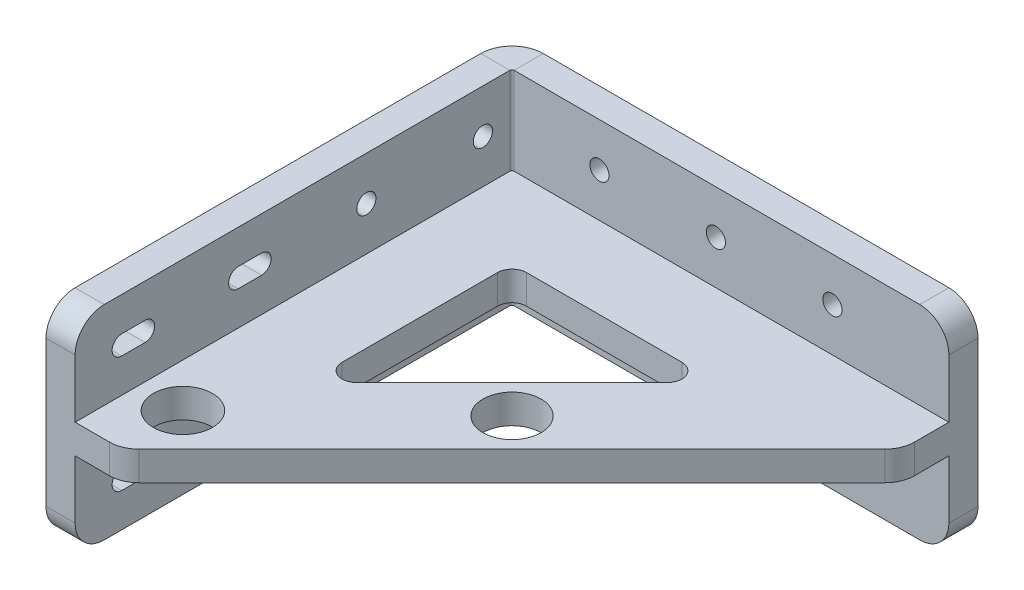
SolidWorks part; units mm, degrees
note: The reader was unsure of these and kept them because the rebuilt part matched: thickness of "基体-法兰1", "边线-法兰1", "钣金6", "钣金7", "钣金8", "钣金9", "钣金10", "钣金11", "钣金12"; flange length of "边线-法兰1".
ref_plane "前视基准面" through (0, 0, 0) normal (0, 0, 1) x (1, 0, 0)
ref_plane "上视基准面" through (0, 0, 0) normal (0, 1, 0) x (1, 0, 0)
ref_plane "右视基准面" through (0, 0, 0) normal (1, 0, 0) x (0, 0, -1)
sketch "草图1" plane through (0, 0, 0) normal (0, 0, 1) x (1, 0, 0)
  line L1 (-80, 35) -> (80, 35)
  line L2 (-80, 35) -> (-80, -35)
  line L3 (-80, -35) -> (80, -35)
  line L4 (80, 35) -> (80, -35)
  line L5 (-80, 35) -> (80, -35) construction
  line L6 (-80, -35) -> (80, 35) construction
  point P0 (0, 0)
  dimension "D1" = 160
  dimension "D2" = 70
base flange "基体-法兰1" sketch "草图1" thickness 10 reverse thickness direction no parameters "D1"=0.7366
edge flange "边线-法兰1" sketch "草图8" flange angle 90 flange length 160 flange position material inside bend radius 0.7366 thickness 10 relief rectangular parameters "D6"=10
sketch "草图8" plane through (-80, 0, 0) normal (-1, 0, 0) x (0, -1, 0)
  line L0 (-35, 0) -> (35, 0) construction
  line L1 (-35, 0) -> (35, 0)
  line L2 (-35, 0) -> (-35, 150)
  line L3 (-35, 150) -> (35, 150)
  line L4 (35, 150) -> (35, 0)
bend "边线折弯1" bend radius 0.7366 bend angle 90 parameters "D5"=1
sketch "草图9" plane through (0, 0, 0) normal (0, 1, 0) x (1, 0, 0)
  line L0 (-70, -150) -> (-54, -150)
  line L1 (-54, -150) -> (80, -16)
  line L2 (80, 0) -> (80, -16)
  line L3 (80, 0) -> (-69.2634, 0) construction
  line L4 (-70, -150) -> (-70, -0.7366) construction
  line L5 (80, 0) -> (-69.2634, 0)
  line L6 (-70, -150) -> (-70, -0.7366)
  arc A0 (-69.2634, 0) -> (-70, -0.7366) centre (-69.2634, -0.7366) ccw construction
  arc A1 (-69.2634, 0) -> (-70, -0.7366) centre (-69.2634, -0.7366) ccw
  dimension "D1" = 16
extrude "凸台-拉伸1" add sketch "草图9" along normal mid plane 10
fillet "圆角1" radius 10 6 edges at (80, -35, -5) (80, 35, -5) (-75, -35, 150) (-75, 35, 150) (80, 0, 16) (-54, 0, 150)
sketch "草图10" plane through (0, 5, 0) normal (0, 1, 0) x (1, 0, 0)
  line L10 (-42, -98.402) -> (28.402, -28)
  line L11 (28.402, -28) -> (-42, -28)
  line L12 (-42, -28) -> (-42, -98.402)
  line L13 (-42, -98.402) -> (28.402, -28)
  line L14 (28.402, -28) -> (-42, -28)
  line L15 (-42, -28) -> (-42, -98.402)
  dimension "D1" = 28
extrude "切除-拉伸1" cut sketch "草图10" against normal blind 10 normal cut yes
fillet "圆角2" radius 5 3 edges at (28.402, 0, 28) (-42, 0, 28) (-42, 0, 98.402)
sketch "草图11" plane through (-70, 0, 0) normal (1, 0, 0) x (0, 0, -1)
  line L0 (10, 35.5) -> (10, 25.4) construction
  line L1 (-70, 35.5) -> (-70, 25.4) construction
  line L2 (10, 35.5) -> (10, 25.4) construction
  line L3 (-70, 35.5) -> (-70, 25.4) construction
  line L4 (-125.9, 40) -> (-125.9, -790) construction
  line L5 (-134.1, 40) -> (-134.1, -790) construction
  line L6 (-94.1, 40) -> (-94.1, -790) construction
  line L7 (-85.9, 40) -> (-85.9, -790) construction
  line L8 (-125.9, 35) -> (-125.9, -35) construction
  line L9 (-134.1, 35) -> (-134.1, -35) construction
  line L10 (-94.1, 35) -> (-94.1, -35) construction
  line L11 (-85.9, 35) -> (-85.9, -35) construction
  line L12 (-70, 30.45) -> (10, 30.45) construction
  line L13 (-0.7366, -35) -> (-140, -35) construction
  line L14 (-140, 35) -> (-0.7366, 35) construction
  line L15 (-134.1, 0) -> (-125.9, 0) construction
  line L16 (-94.1, 0) -> (-85.9, 0) construction
  line L17 (-30, 30.45) -> (-30, 0) construction
  line L18 (0, 0) -> (-30, 0) construction
  line L19 (-130, -20) -> (-130, 20) construction
  line L20 (-90, -20) -> (-90, 20) construction
  line L21 (-10, 0) -> (-50, 0) construction
  line L22 (-50, -20) -> (-50, 20) construction
  line L23 (-10, -20) -> (-10, 20) construction
  line L24 (-134, 20) -> (-126, 20) construction
  line L25 (-134, 23.3) -> (-126, 23.3)
  line L26 (-134, 16.7) -> (-126, 16.7)
  line L27 (-86, 20) -> (-94, 20) construction
  line L28 (-86, 16.7) -> (-94, 16.7)
  line L29 (-86, 23.3) -> (-94, 23.3)
  line L30 (-86, -20) -> (-94, -20) construction
  line L31 (-86, -23.3) -> (-94, -23.3)
  line L32 (-86, -16.7) -> (-94, -16.7)
  line L33 (-126, -20) -> (-134, -20) construction
  line L34 (-126, -23.3) -> (-134, -23.3)
  line L35 (-126, -16.7) -> (-134, -16.7)
  circle A0 centre (-50, 20) radius 3.3
  circle A1 centre (-10, 20) radius 3.3
  circle A2 centre (-10, -20) radius 3.3
  circle A3 centre (-50, -20) radius 3.3
  arc A4 (-134, 23.3) -> (-134, 16.7) centre (-134, 20) ccw
  arc A5 (-126, 16.7) -> (-126, 23.3) centre (-126, 20) ccw
  arc A6 (-86, 16.7) -> (-86, 23.3) centre (-86, 20) ccw
  arc A7 (-94, 23.3) -> (-94, 16.7) centre (-94, 20) ccw
  arc A8 (-86, -23.3) -> (-86, -16.7) centre (-86, -20) ccw
  arc A9 (-94, -16.7) -> (-94, -23.3) centre (-94, -20) ccw
  arc A10 (-126, -23.3) -> (-126, -16.7) centre (-126, -20) ccw
  arc A11 (-134, -16.7) -> (-134, -23.3) centre (-134, -20) ccw
  point P32 (-130, 0)
  point P40 (-90, 0)
  point P43 (-30, 0)
  point P46 (-50, 0)
  point P49 (-10, 0)
  point P55 (-130, 20)
  point P61 (-90, 20)
  point P68 (-90, -20)
  point P75 (-130, -20)
  dimension "D3" = 6.6
  dimension "D1" = 40
  dimension "D2" = 40
  dimension "D4" = 6.6
  dimension "D5" = 8
extrude "切除-拉伸2" cut sketch "草图11" against normal blind 10 normal cut yes
sketch "草图12" plane through (0, 0, 0) normal (0, 0, 1) x (1, 0, 0)
  line L0 (40, 0) -> (-40, 0) construction
  line L1 (-40, -20) -> (-40, 20) construction
  line L2 (40, -20) -> (40, 20) construction
  line L3 (0, -20) -> (0, 20) construction
  circle A0 centre (-40, -20) radius 3.3
  circle A1 centre (-40, 20) radius 3.3
  circle A2 centre (40, 20) radius 3.3
  circle A3 centre (40, -20) radius 3.3
  circle A4 centre (0, -20) radius 3.3
  circle A5 centre (0, 20) radius 3.3
  point P4 (0, 0)
  point P8 (-40, 0)
  point P11 (40, 0)
  point P18 (0, 0)
  dimension "D3" = 6.6
  dimension "D1" = 80
  dimension "D2" = 40
extrude "切除-拉伸3" cut sketch "草图12" against normal blind 10 normal cut yes
sketch "草图13" plane through (0, 5, 0) normal (0, 1, 0) x (1, 0, 0)
  line L2 (-6.799, -63.201) -> (13, -83) construction
  line L3 (-33.4645, -89.8665) -> (19.8665, -36.5355) construction
  line L4 (-51.0711, -147.0711) -> (77.0711, -18.9289) construction
  line L5 (-80, -140) -> (-80, -0.7366) construction
  line L6 (-70, -150) -> (-58.1421, -150) construction
  circle A0 centre (3.1005, -73.1005) radius 10
  circle A1 centre (-55, -128) radius 10.1516
  point P2 (-57.4709, -128.7744)
  dimension "D2" = 25
  dimension "D3" = 20
  dimension "D1" = 20.3033
  dimension "D4" = 22
extrude "切除-拉伸4" cut sketch "草图13" against normal blind 10
sketch "折弯-线1" plane through (0, 0, 0) normal (0, 1, 0) x (1, 0, 0)
sketch "边界框1" plane through (0, 0, 0) normal (0, 1, 0) x (1, 0, 0)
sheet metal parameters "钣金6" thickness 10 parameters "D1"=0.7366, "D7"=5
flat pattern "平板型式6" [suppressed]
sketch "折弯-线2" plane through (0, 0, 0) normal (0, 1, 0) x (1, 0, 0)
sketch "边界框2" [suppressed] plane through (0, 0, 0) normal (0, 1, 0) x (1, 0, 0)
sheet metal parameters "钣金7" thickness 10 parameters "D1"=0.7366, "D7"=5
flat pattern "平板型式6" [suppressed]
sketch "折弯-线2" plane through (0, 0, 0) normal (0, 1, 0) x (1, 0, 0)
sketch "边界框2" [suppressed] plane through (0, 0, 0) normal (0, 1, 0) x (1, 0, 0)
bend of the flat pattern "展平-<边线折弯1>1"
sheet metal parameters "钣金8" thickness 10 parameters "D1"=0.7366, "D7"=5
flat pattern "平板型式6" [suppressed]
sketch "折弯-线2" plane through (0, 0, 0) normal (0, 1, 0) x (1, 0, 0)
sketch "边界框2" [suppressed] plane through (0, 0, 0) normal (0, 1, 0) x (1, 0, 0)
bend of the flat pattern "展平-<边线折弯1>1"
sheet metal parameters "钣金9" thickness 10 parameters "D1"=0.7366, "D7"=5
flat pattern "平板型式6" [suppressed]
sketch "折弯-线2" plane through (0, 0, 0) normal (0, 1, 0) x (1, 0, 0)
sketch "边界框2" [suppressed] plane through (0, 0, 0) normal (0, 1, 0) x (1, 0, 0)
bend of the flat pattern "展平-<边线折弯1>1"
sheet metal parameters "钣金10" thickness 10 parameters "D1"=0.7366, "D7"=5
flat pattern "平板型式6" [suppressed]
sketch "折弯-线2" plane through (0, 0, 0) normal (0, 1, 0) x (1, 0, 0)
sketch "边界框2" [suppressed] plane through (0, 0, 0) normal (0, 1, 0) x (1, 0, 0)
bend of the flat pattern "展平-<边线折弯1>1"
sheet metal parameters "钣金11" thickness 10 parameters "D1"=0.7366, "D7"=5
flat pattern "平板型式6" [suppressed]
sketch "折弯-线2" plane through (0, 0, 0) normal (0, 1, 0) x (1, 0, 0)
sketch "边界框2" [suppressed] plane through (0, 0, 0) normal (0, 1, 0) x (1, 0, 0)
bend of the flat pattern "展平-<边线折弯1>1"
sheet metal parameters "钣金12" thickness 10 parameters "D1"=0.7366, "D7"=5
flat pattern "平板型式6" [suppressed]
sketch "折弯-线2" plane through (0, 0, 0) normal (0, 1, 0) x (1, 0, 0)
sketch "边界框2" [suppressed] plane through (0, 0, 0) normal (0, 1, 0) x (1, 0, 0)
bend of the flat pattern "展平-<边线折弯1>1"
